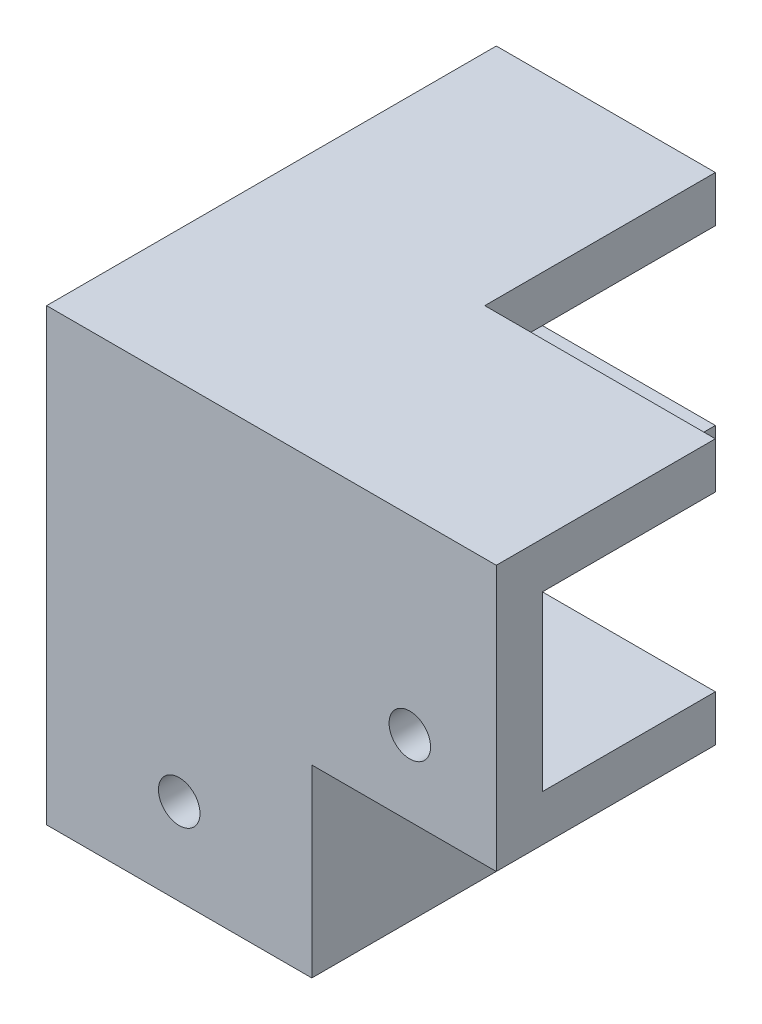
SolidWorks part; units mm, degrees
ref_plane "前视基准面" through (0, 0, 0) normal (0, 0, 1) x (1, 0, 0)
ref_plane "上视基准面" through (0, 0, 0) normal (0, 1, 0) x (1, 0, 0)
ref_plane "右视基准面" through (0, 0, 0) normal (1, 0, 0) x (0, 0, -1)
sketch "草图1" plane through (0, 0, 0) normal (0, 1, 0) x (1, 0, 0)
  line L0 (8.9733, 0.9097) -> (8.9733, -3.0903)
  line L1 (-6.0267, 0.9097) -> (8.9733, 0.9097)
  line L2 (-10.0267, 0.496) -> (-10.0267, -3.0903)
  line L3 (-10.0267, -3.0903) -> (8.9733, -3.0903)
  line L6 (-10.0267, 0.496) -> (-10.0267, 19.9097)
  line L7 (-10.0267, 19.9097) -> (-4.5733, 19.9097)
  line L8 (-6.0267, 0.9097) -> (-6.0267, 15.9097)
  line L13 (-4.5733, 19.9097) -> (8.9733, 19.9097)
  line L15 (-6.0267, 15.9097) -> (8.9733, 15.9097)
  line L16 (8.9733, 19.9097) -> (8.9733, 15.9097)
  dimension "D1" = 4
  dimension "D3" = 4
  dimension "D4" = 15
  dimension "D5" = 15
  dimension "D6" = 4
extrude "凸台-拉伸1" add sketch "草图1" along normal blind 20 contours L16 L13 L7 L6 L2 L3 L1 L8 L15 region at (8.675, 0, 1.0903)
sketch "草图2" plane through (8.9733, 0, 0) normal (1, 0, 0) x (0, 0, -1)
  line L1 (-3.0903, 20) -> (15.8097, 20)
  line L2 (-3.0903, 20) -> (-3.0903, 0)
  line L3 (-3.0903, 0) -> (15.8097, 0)
  line L4 (15.8097, 20) -> (15.8097, 0)
  dimension "D1" = 18.9
extrude "凸台-拉伸2" add sketch "草图2" along normal blind 4 separate body
sketch "草图3" plane through (-10.0267, 0, 0) normal (-1, 0, 0) x (0, 0, 1)
  line L1 (3.0903, 20) -> (-0.9097, 20)
  line L2 (3.0903, 20) -> (3.0903, 39)
  line L3 (3.0903, 39) -> (-0.9097, 39)
  line L4 (-0.9097, 20) -> (-0.9097, 39)
  line L5 (-0.9097, 39) -> (-15.9097, 39)
  line L6 (-0.9097, 39) -> (-0.9097, 35)
  line L7 (-0.9097, 35) -> (-15.9097, 35)
  line L8 (-15.9097, 39) -> (-15.9097, 35)
  line M7 (3.0903, 20) -> (-19.9097, 20)
  dimension "D1" = 4
  dimension "D2" = 4
  dimension "D3" = 15
  dimension "D4" = 15
extrude "凸台-拉伸3" add sketch "草图3" against normal blind 39 contours L5 L8 L7 L4 | L4 L2 L3 M7 region at (-10.0267, 29.5, 1.0903) region at (-10.0267, 37, -8.4097)
sketch "草图4" plane through (12.9733, 0, 0) normal (1, 0, 0) x (0, 0, -1)
  line L1 (-3.0903, 20) -> (15.9097, 20)
  line L2 (-3.0903, 20) -> (-3.0903, 16)
  line L3 (-3.0903, 16) -> (15.9097, 16)
  line L4 (15.9097, 20) -> (15.9097, 16)
  dimension "D1" = 4
  dimension "D2" = 19
extrude "凸台-拉伸4" add sketch "草图4" along normal blind 16
sketch "草图5" plane through (0, 0, -15.9097) normal (0, 0, -1) x (-1, 0, 0)
  line L0 (-28.9733, 39) -> (10.0267, 39) construction
  line L1 (10.0267, 35) -> (-8.9733, 35)
  line L2 (10.0267, 35) -> (10.0267, 39)
  line L3 (10.0267, 39) -> (-8.9733, 39)
  line L4 (-8.9733, 35) -> (-8.9733, 39)
  line L6 (10.0267, 35) -> (6.0267, 35)
  line L7 (10.0267, 35) -> (10.0267, 20)
  line L8 (10.0267, 20) -> (6.0267, 20)
  line L9 (6.0267, 35) -> (6.0267, 20)
  line M4 (10.0267, 35) -> (10.0267, 39)
  line M5 (10.0267, 39) -> (-28.9733, 39)
  line M7 (-28.9733, 35) -> (10.0267, 35)
  dimension "D1" = 19
  dimension "D2" = 15
  dimension "D3" = 4
extrude "凸台-拉伸5" add sketch "草图5" along normal blind 20 and the other way blind 15 contours L4 L1 M7 M4 M5 | L1 L9 L8 L7 region at (-8.0267, 27.5, -15.9097) region at (-0.5267, 37, -15.9097)
sketch "草图6" plane through (0, 0, -19.9097) normal (0, 0, -1) x (-1, 0, 0)
  line L0 (-8.9733, 20) -> (-8.9733, 0) construction
  line L1 (10.0267, 20) -> (-8.9733, 20)
  line L2 (10.0267, 20) -> (10.0267, 16)
  line L3 (10.0267, 16) -> (-8.9733, 16)
  line L4 (-8.9733, 20) -> (-8.9733, 16)
  dimension "D1" = 4
extrude "凸台-拉伸6" add sketch "草图6" along normal blind 16
sketch "草图7" plane through (0, 0, 3.0903) normal (0, 0, 1) x (1, 0, 0)
  line L0 (28.9733, 16) -> (28.9733, 39) construction
  circle A0 centre (21.4733, 22.5) radius 1.8
  dimension "D1" = 3.6
  dimension "D2" = 7.5
extrude "切除-拉伸1" cut sketch "草图7" against normal blind 16
sketch "草图8" plane through (-10.0267, 0, 0) normal (-1, 0, 0) x (0, 0, 1)
  line L0 (-35.9097, 16) -> (-35.9097, 39) construction
  line L1 (3.0903, 0) -> (-19.9097, 0) construction
  circle A0 centre (-28.4097, 22.5) radius 1.8
  circle A1 centre (-8.4097, 7.5) radius 1.8
  dimension "D1" = 3.6
  dimension "D2" = 3.6
  dimension "D3" = 7.5
  dimension "D4" = 7.5
extrude "切除-拉伸2" cut sketch "草图8" against normal blind 16
sketch "草图9" plane through (0, 0, 3.0903) normal (0, 0, 1) x (1, 0, 0)
  line L0 (-10.0267, 0) -> (12.9733, 0) construction
  circle A0 centre (1.4733, 7.5) radius 1.8
  dimension "D1" = 3.6
  dimension "D2" = 7.5
extrude "切除-拉伸3" cut sketch "草图9" against normal blind 16
